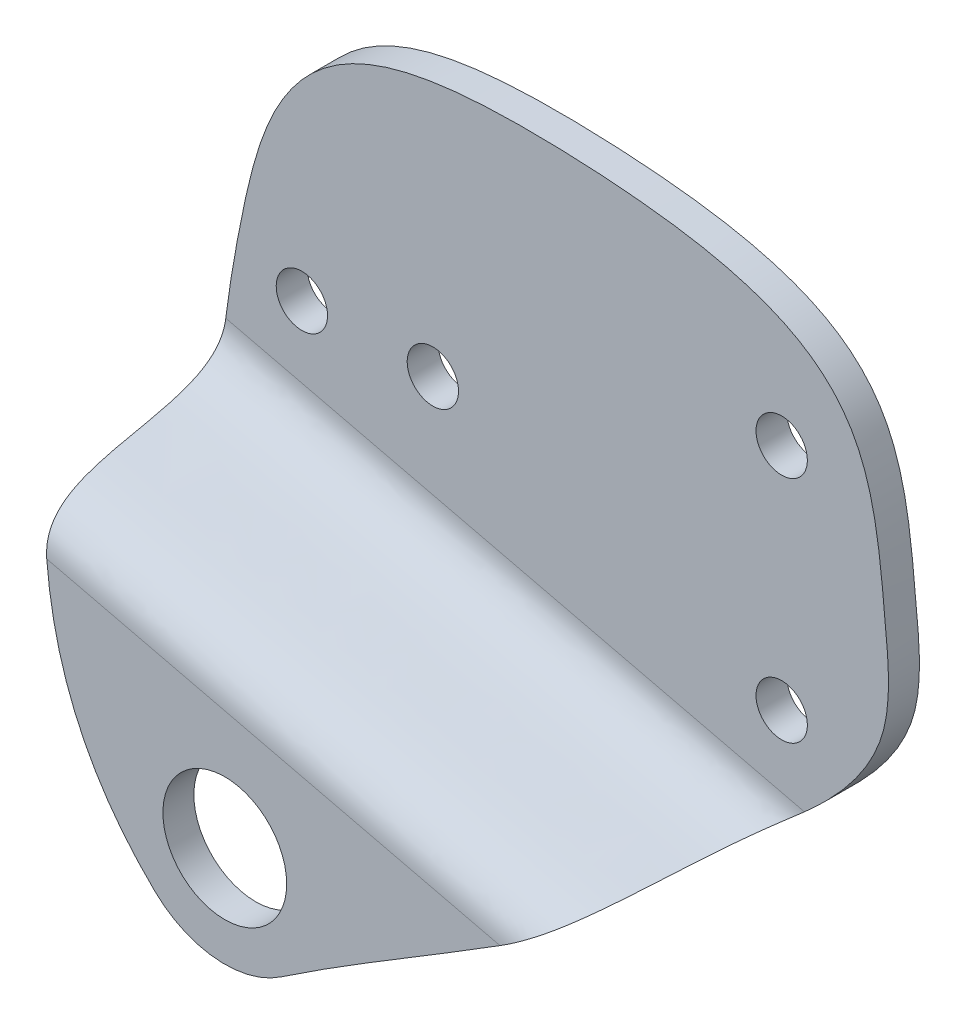
SolidWorks part; units mm, degrees
material "ABS"
ref_plane "Front Plane" through (0, 0, 0) normal (0, 0, 1) x (1, 0, 0)
ref_plane "Top Plane" through (0, 0, 0) normal (0, 1, 0) x (1, 0, 0)
ref_plane "Right Plane" through (0, 0, 0) normal (1, 0, 0) x (0, 0, -1)
sketch "main_features_sketch" plane through (0, 0, 0) normal (0, 0, 1) x (1, 0, 0)
  line L0 (0, -7.3) -> (0, 0) construction
  line L1 (-127, -19.05) -> (127, -19.05) construction
  line L2 (-12.0493, -9.2395) -> (15.4719, -35.7057) construction
  line L3 (-1.2057, -19.8915) -> (-35.1292, -42.8629) construction
  circle A0 centre (-9.525, 25.4) radius 6 construction
  circle A1 centre (3.175, 25.4) radius 6 construction
  circle A2 centre (37, 36.5125) radius 6 construction
  circle A3 centre (37, 14.2875) radius 6 construction
  circle A4 centre (0, -7.3) radius 6
  circle A5 centre (0, -7.3) radius 9.75
  circle A6 centre (-9.525, 25.4) radius 2.4892
  circle A7 centre (3.175, 25.4) radius 2.4892
  circle A8 centre (37, 36.5125) radius 2.4892
  circle A9 centre (37, 14.2875) radius 2.4892
  spline S0 degree 3 poles (-6.7583, -14.3277) (-19.8154, -1.7711) (-17.8681, 18.3746) (-11.5594, 47.1139) (0.7713, 51.6537) (45.1342, 49.0484) (46.0113, 37.2911) (48.8462, 7.8731) (21.9825, -4.1895) (5.4668, -15.3732) knots 0 0 0 0 0.179468 0.221834 0.401236 0.45577 0.712637 0.770271 1 1 1 1
  dimension "D1" = 12
  dimension "D2" = 19.5
  dimension "D4" = 12
  dimension "D5" = 4.9784
  dimension "D3" = 2
extrude "Boss-Extrude1" add sketch "main_features_sketch" along normal blind 20 contours S0 A5 A9 A8 A7 A6 | A5 A4 region at (8.3693, -11.7403, 0) region at (14.0249, 22.7845, 0)
ref_plane "Plane1" through (4.647, 19.4558, 0) normal (0.2323, 0.9726, 0) x (0.9726, -0.2323, 0)
ref_plane "cut_plane" through (-12.3292, 2.9448, 0) normal (-0.9726, 0.2323, 0) x (0, 0, 1)
sketch "Sketch2" plane through (-12.676, 1.4928, 0) normal (0.9726, -0.2323, 0) x (0, 0, -1)
  line L0 (-3, 56.3464) -> (-3, 17.2679)
  line L1 (-20, -15.3574) -> (-20, 5.6129)
  line L3 (0, -14.0129) -> (0, 56.3464) construction
  line L4 (-20, 2.5676) -> (-20, 15.7103) construction
  line L5 (-3, 22.2829) -> (-3, 34.5715) construction
  line L6 (0, 56.3464) -> (0, 15.4609)
  line L7 (-17, 4.54) -> (-17, -15.3574)
  line L8 (-20, -15.3574) -> (0, -15.3574) construction
  line L9 (0, 56.3464) -> (-20, 56.3464) construction
  line L10 (-3, 56.3464) -> (0, 56.3464)
  line L11 (-17, -15.3574) -> (-20, -15.3574)
  line L12 (-17, 0.1846) -> (-17, 6.182) construction
  line L13 (0, 2.2857) -> (0, 6.7648) construction
  line L14 (0, 15.4609) -> (0, -15.3574)
  line L15 (0, -15.3574) -> (-17, -15.3574)
  line L16 (-20, 5.6129) -> (-20, 56.3464)
  line L17 (-20, 56.3464) -> (-3, 56.3464)
  spline S0 degree 3 poles (-3, 17.2679) (-3, 9.5875) (-20, 13.8271) (-20, 5.6129) knots 0 0 0 0 1 1 1 1
  spline S1 degree 3 poles (0, 15.4609) (0, 9.0167) (-17, 7.0389) (-17, 4.54) knots 0 0 0 0 1 1 1 1
  point P21 (0, 0)
  point P26 (0, 10.6276)
  point P28 (0, 0)
  point P31 (0, 0)
  point P32 (0, 0)
  point P33 (0, 0)
  point P35 (0, 0)
  dimension "D2" = 3
extrude "Cut-Extrude1" cut sketch "Sketch2" against normal through all both and the other way through all contours L0 S0 L16 L17 | S1 L14 L15 L7 region at (-4.7924, 34.4994, 11.6965) region at (-13.4102, -1.581, 8.0397)
